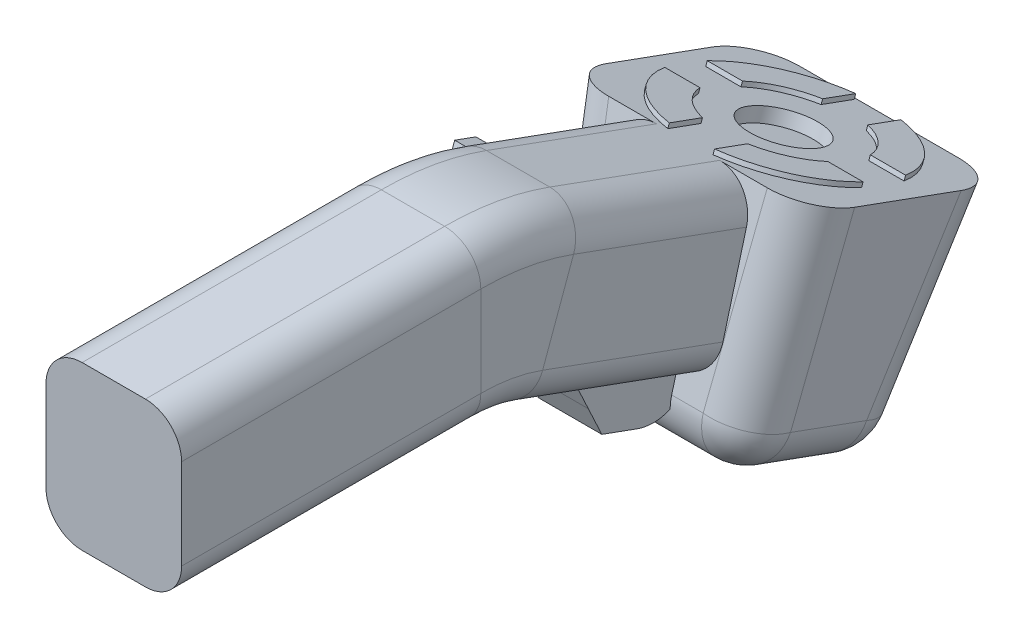
SolidWorks part; units mm, degrees
ref_plane "Front Plane" through (0, 0, 0) normal (0, 0, 1) x (1, 0, 0)
ref_plane "Top Plane" through (0, 0, 0) normal (0, 1, 0) x (1, 0, 0)
ref_plane "Right Plane" through (0, 0, 0) normal (1, 0, 0) x (0, 0, -1)
sketch "Sketch2" plane through (0, 0, 0) normal (1, 0, 0) x (0, 0, -1)
  line L0 (0, 0) -> (66.1837, 0)
  line L1 (83.2847, -3.0154) -> (136.08, -22.2313)
  arc A0 (66.1837, 0) -> (83.2847, -3.0154) centre (66.1837, -50) cw
  point P5 (75, 0)
  dimension "D4" = 50
  dimension "D1" = 75
  dimension "D2" = 65
  dimension "D3" = 160
sketch "Sketch1" plane through (0, 0, 0) normal (0, 0, 1) x (1, 0, 0)
  line L1 (7, -18) -> (-7, -18)
  line L2 (15, -10) -> (15, 10)
  line L3 (7, 18) -> (-7, 18)
  line L4 (-15, -10) -> (-15, 10)
  line L5 (15, -18) -> (-15, 18) construction
  line L6 (15, 18) -> (-15, -18) construction
  arc A1 (15, 10) -> (7, 18) centre (7, 10) ccw
  arc A2 (-7, 18) -> (-15, 10) centre (-7, 10) ccw
  arc A3 (-7, -18) -> (-15, -10) centre (-7, -10) cw
  arc A4 (7, -18) -> (15, -10) centre (7, -10) ccw
  point P0 (0, 0)
  dimension "D1" = 30
  dimension "D3" = 8
  dimension "D2" = 36
sweep "Sweep1" add profiles "Sketch1" path "Sketch2"
sketch "Sketch3" plane through (0, 7.1901, -2.617) normal (0, -0.9397, 0.342) x (1, 0, 0)
  line L0 (-7, -79.2933) -> (-7, -135.4769) construction
  line L1 (7, -131.2933) -> (-7, -131.2933)
  line L2 (7, -131.2933) -> (7, -103.2933)
  line L3 (7, -103.2933) -> (-7, -103.2933)
  line L4 (-7, -131.2933) -> (-7, -103.2933)
  line L5 (7, -131.2933) -> (-7, -103.2933) construction
  line L6 (7, -103.2933) -> (-7, -131.2933) construction
  line L7 (7, -79.2933) -> (7, -135.4769) construction
  line L8 (-7, -79.2933) -> (7, -79.2933) construction
  point P0 (0, -117.2933)
  dimension "D1" = 24
  dimension "D2" = 28
extrude "Boss-Extrude1" add sketch "Sketch3" along normal blind 10
chamfer "Chamfer1" distance 5 angle 45 2 edges at (0, -37.5352, -96.2607) (0, -28.1383, -99.6809)
sketch "Sketch4" plane through (0, -2.2069, 0.8032) normal (0, -0.9397, 0.342) x (1, 0, 0)
  line L0 (-7, -131.2933) -> (7, -131.2933) construction
  line L1 (7, -131.2933) -> (-7, -131.2933)
  line L2 (7, -131.2933) -> (7, -121.2933)
  line L3 (7, -121.2933) -> (-7, -121.2933)
  line L4 (-7, -131.2933) -> (-7, -121.2933)
  line L5 (-7, -108.2933) -> (-7, -131.2933) construction
  dimension "D1" = 10
extrude "Cut-Extrude1" cut sketch "Sketch4" against normal blind 5
fillet "Fillet1" radius 10 1 edges at (0, -38.9931, -114.8853)
fillet "Fillet2" radius 10 1 edges at (0, -43.6916, -113.1752)
sketch "Sketch5" plane through (0, 41.019, -14.9297) normal (0, 0.9397, -0.342) x (1, 0, 0)
  line L0 (7, 79.2933) -> (-7, 79.2933) construction
  line L1 (27.5, 164.2933) -> (-27.5, 164.2933)
  line L2 (27.5, 164.2933) -> (27.5, 119.2933)
  line L3 (27.5, 119.2933) -> (-27.5, 119.2933)
  line L4 (-27.5, 164.2933) -> (-27.5, 119.2933)
  line L6 (7, 135.4769) -> (-7, 135.4769) construction
  point P6 (0, 164.2933)
  point P8 (0, 79.2933)
  point P10 (0, 135.4769)
  dimension "D1" = 45
  dimension "D2" = 55
  dimension "D3" = 40
  dimension "D5" = 27.5
extrude "Boss-Extrude2" add sketch "Sketch5" against normal blind 50 draft 5
sketch "Sketch6" plane through (-15, 0, 0) normal (-1, 0, 0) x (0, 0, 1)
  line L0 (-107.6589, -22.5287) -> (-93.5635, -17.3984)
  line L1 (-107.6589, -22.5287) -> (-114.4993, -3.7348)
  line L2 (-93.5635, -17.3984) -> (-100.4039, 1.3955)
  line L3 (-114.4993, -3.7348) -> (-100.4039, 1.3955)
  line L4 (-79.8645, -12.4123) -> (-119.7541, -26.9309) construction
  line L5 (-86.7049, 6.3816) -> (-124.9503, -7.5386) construction
  line L6 (-86.7049, 6.3816) -> (-79.8645, -12.4123) construction
  dimension "D1" = 15
  dimension "D2" = 14.5783
extrude "Boss-Extrude3" add sketch "Sketch6" along normal blind 10
chamfer "Chamfer2" distance 10 angle 45 1 edges at (-20, -3.7348, -114.4993)
sketch "Sketch7" plane through (0, 41.019, -14.9297) normal (0, 0.9397, -0.342) x (1, 0, 0)
  line L0 (27.5, 119.2933) -> (27.5, 164.2933) construction
  line L1 (27.5, 164.2933) -> (-27.5, 164.2933) construction
  circle A0 centre (0, 141.7933) radius 8
  point P2 (0, 0)
  point P5 (27.5, 141.7933)
  point P8 (0, 164.2933)
  dimension "D1" = 16
extrude "Cut-Extrude2" cut sketch "Sketch7" against normal blind 3 contours A0
sketch "Sketch10" plane through (0, 41.019, -14.9297) normal (0, 0.9397, -0.342) x (1, 0, 0)
  line L0 (14.1421, 136.7933) -> (21.9374, 136.7933)
  line L2 (-5, 119.8559) -> (-5, 127.6512)
  line L4 (5, 119.8559) -> (5, 127.6512)
  line L7 (-21.9374, 136.7933) -> (-14.1421, 136.7933)
  line L9 (-21.9374, 146.7933) -> (-14.1421, 146.7933)
  line L13 (14.1421, 146.7933) -> (21.9374, 146.7933)
  line L14 (5, 155.9354) -> (5, 163.7307)
  line L17 (-5, 155.9354) -> (-5, 163.7307)
  arc A0 (14.1421, 146.7933) -> (5, 155.9354) centre (0, 141.7933) ccw
  circle A1 centre (0, 141.7933) radius 8 construction
  arc A2 (5, 119.8559) -> (21.9374, 136.7933) centre (0, 141.7933) ccw
  arc A3 (5, 127.6512) -> (14.1421, 136.7933) centre (0, 141.7933) ccw
  arc A4 (21.9374, 146.7933) -> (5, 163.7307) centre (0, 141.7933) ccw
  arc A5 (-14.1421, 136.7933) -> (-5, 127.6512) centre (0, 141.7933) ccw
  arc A6 (-21.9374, 136.7933) -> (-5, 119.8559) centre (0, 141.7933) ccw
  arc A7 (-5, 155.9354) -> (-14.1421, 146.7933) centre (0, 141.7933) ccw
  arc A8 (-5, 163.7307) -> (-21.9374, 146.7933) centre (0, 141.7933) ccw
  dimension "D1" = 30
  dimension "D2" = 45
  dimension "D3" = 10
  dimension "D4" = 10
  dimension "D5" = 10
  dimension "D6" = 10
extrude "Boss-Extrude4" add sketch "Sketch10" along normal blind 1
fillet "Fillet3" radius 10 8 edges at (0, -60.6611, -148.1033) (-23.1256, -54.4618, -131.0708) (0, -48.2625, -114.0383) (23.1256, -54.4618, -131.0708) (25.3128, -37.9169, -158.7091) (25.3128, -24.0221, -120.5335) (-25.3128, -24.0221, -120.5335) (-25.3128, -37.9169, -158.7091)
equation "\"D4@Sketch10\"=\"D3@Sketch10\""
equation "\"D5@Sketch10\"=\"D3@Sketch10\""
equation "\"D6@Sketch10\"=\"D3@Sketch10\""
